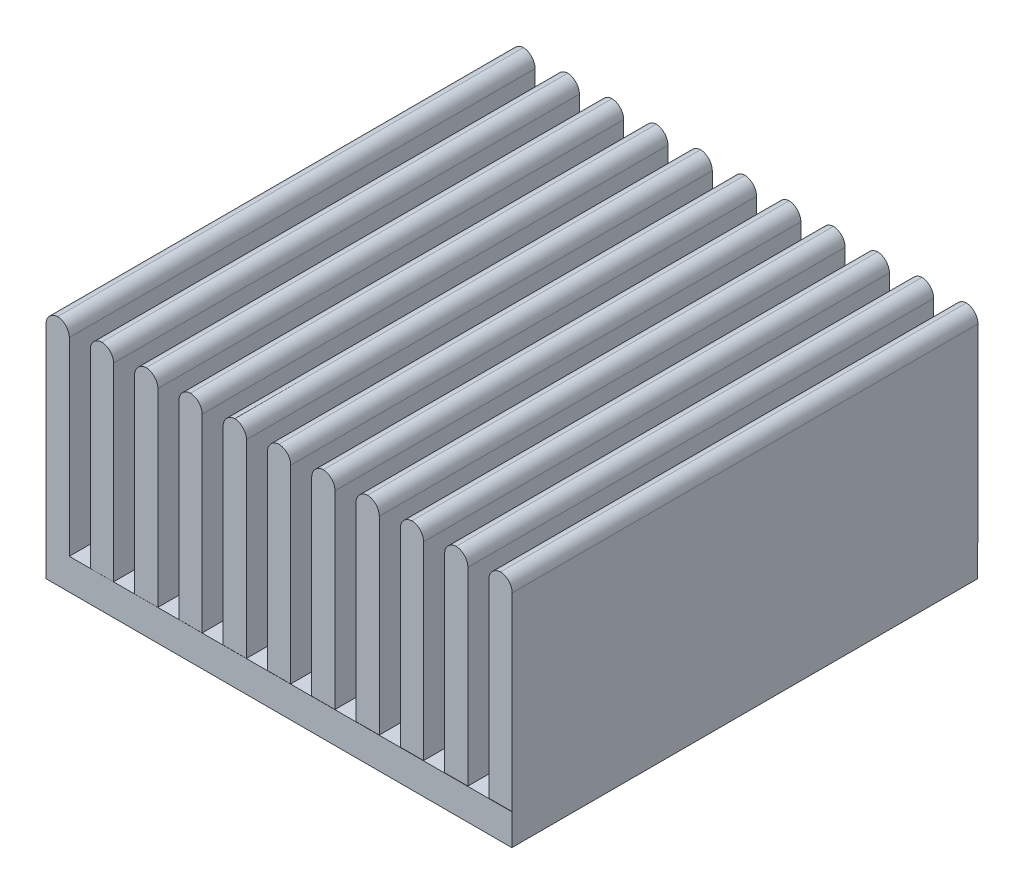
SolidWorks part; units mm, degrees
material "1100-H16 Rod (SS)"
ref_plane "Front Plane" through (0, 0, 0) normal (0, 0, 1) x (1, 0, 0)
ref_plane "Top Plane" through (0, 0, 0) normal (0, 1, 0) x (1, 0, 0)
ref_plane "Right Plane" through (0, 0, 0) normal (1, 0, 0) x (0, 0, -1)
sketch "Sketch1" plane through (0, 0, 0) normal (0, 1, 0) x (1, 0, 0)
  line L1 (-19.05, -19.05) -> (19.05, -19.05)
  line L2 (-19.05, -19.05) -> (-19.05, 19.05)
  line L3 (-19.05, 19.05) -> (19.05, 19.05)
  line L4 (19.05, -19.05) -> (19.05, 19.05)
  line L5 (-19.05, -19.05) -> (19.05, 19.05) construction
  line L6 (-19.05, 19.05) -> (19.05, -19.05) construction
  point P0 (0, 0)
  dimension "D1" = 38.1
  dimension "D2" = 38.1
extrude "Boss-Extrude1" add sketch "Sketch1" along normal blind 2.54
sketch "Sketch2" plane through (0, 2.54, 0) normal (0, 1, 0) x (1, 0, 0)
  line L0 (-19.05, -19.05) -> (19.05, -19.05) construction
  line L1 (-19.05, 19.05) -> (-17.145, 19.05)
  line L2 (-19.05, 19.05) -> (-19.05, -19.05)
  line L3 (-19.05, -19.05) -> (-17.145, -19.05)
  line L4 (-17.145, 19.05) -> (-17.145, -19.05)
  line L5 (-15.4305, 19.0526) -> (-15.4305, -19.0474)
  line L6 (-15.4305, 19.0526) -> (-13.5255, 19.0526)
  line L7 (-13.5255, 19.0526) -> (-13.5255, -19.0474)
  line L8 (-15.4305, -19.0474) -> (-13.5255, -19.0474)
  line L9 (-11.811, 19.0552) -> (-11.811, -19.0448)
  line L10 (-11.811, 19.0552) -> (-9.906, 19.0552)
  line L11 (-9.906, 19.0552) -> (-9.906, -19.0448)
  line L12 (-11.811, -19.0448) -> (-9.906, -19.0448)
  line L13 (-8.1915, 19.0578) -> (-8.1915, -19.0422)
  line L14 (-8.1915, 19.0578) -> (-6.2865, 19.0578)
  line L15 (-6.2865, 19.0578) -> (-6.2865, -19.0422)
  line L16 (-8.1915, -19.0422) -> (-6.2865, -19.0422)
  line L17 (-4.572, 19.0605) -> (-4.572, -19.0395)
  line L18 (-4.572, 19.0605) -> (-2.667, 19.0605)
  line L19 (-2.667, 19.0605) -> (-2.667, -19.0395)
  line L20 (-4.572, -19.0395) -> (-2.667, -19.0395)
  line L21 (-0.9525, 19.0631) -> (-0.9525, -19.0369)
  line L22 (-0.9525, 19.0631) -> (0.9525, 19.0631)
  line L23 (0.9525, 19.0631) -> (0.9525, -19.0369)
  line L24 (-0.9525, -19.0369) -> (0.9525, -19.0369)
  line L25 (2.667, 19.0657) -> (2.667, -19.0343)
  line L26 (2.667, 19.0657) -> (4.572, 19.0657)
  line L27 (4.572, 19.0657) -> (4.572, -19.0343)
  line L28 (2.667, -19.0343) -> (4.572, -19.0343)
  line L29 (6.2865, 19.0683) -> (6.2865, -19.0317)
  line L30 (6.2865, 19.0683) -> (8.1915, 19.0683)
  line L31 (8.1915, 19.0683) -> (8.1915, -19.0317)
  line L32 (6.2865, -19.0317) -> (8.1915, -19.0317)
  line L33 (9.906, 19.0709) -> (9.906, -19.0291)
  line L34 (9.906, 19.0709) -> (11.811, 19.0709)
  line L35 (11.811, 19.0709) -> (11.811, -19.0291)
  line L36 (9.906, -19.0291) -> (11.811, -19.0291)
  line L37 (13.5255, 19.0735) -> (13.5255, -19.0265)
  line L38 (13.5255, 19.0735) -> (15.4305, 19.0735)
  line L39 (15.4305, 19.0735) -> (15.4305, -19.0265)
  line L40 (13.5255, -19.0265) -> (15.4305, -19.0265)
  line L41 (17.145, 19.0761) -> (17.145, -19.0239)
  line L42 (17.145, 19.0761) -> (19.05, 19.0761)
  line L43 (19.05, 19.0761) -> (19.05, -19.0239)
  line L44 (17.145, -19.0239) -> (19.05, -19.0239)
  line L45 (19.05, -19.05) -> (19.05, 19.05) construction
  dimension "D2" = 1.905
  dimension "D1" = 11
extrude "Boss-Extrude2" add sketch "Sketch2" along normal blind 16.51
fillet "Fillet3" radius 1.016 22 edges at (-19.05, 19.05, 0) (-17.145, 19.05, 0) (19.05, 19.05, -0.0261) (17.145, 19.05, -0.0261) (15.4305, 19.05, -0.0235) (13.5255, 19.05, -0.0235) (11.811, 19.05, -0.0209) (9.906, 19.05, -0.0209) (8.1915, 19.05, -0.0183) (6.2865, 19.05, -0.0183) (4.572, 19.05, -0.0157) (2.667, 19.05, -0.0157) (0.9525, 19.05, -0.0131) (-0.9525, 19.05, -0.0131) (-2.667, 19.05, -0.0105) (-4.572, 19.05, -0.0105) (-6.2865, 19.05, -0.0078) (-8.1915, 19.05, -0.0078) (-9.906, 19.05, -0.0052) (-11.811, 19.05, -0.0052) (-13.5255, 19.05, -0.0026) (-15.4305, 19.05, -0.0026)
